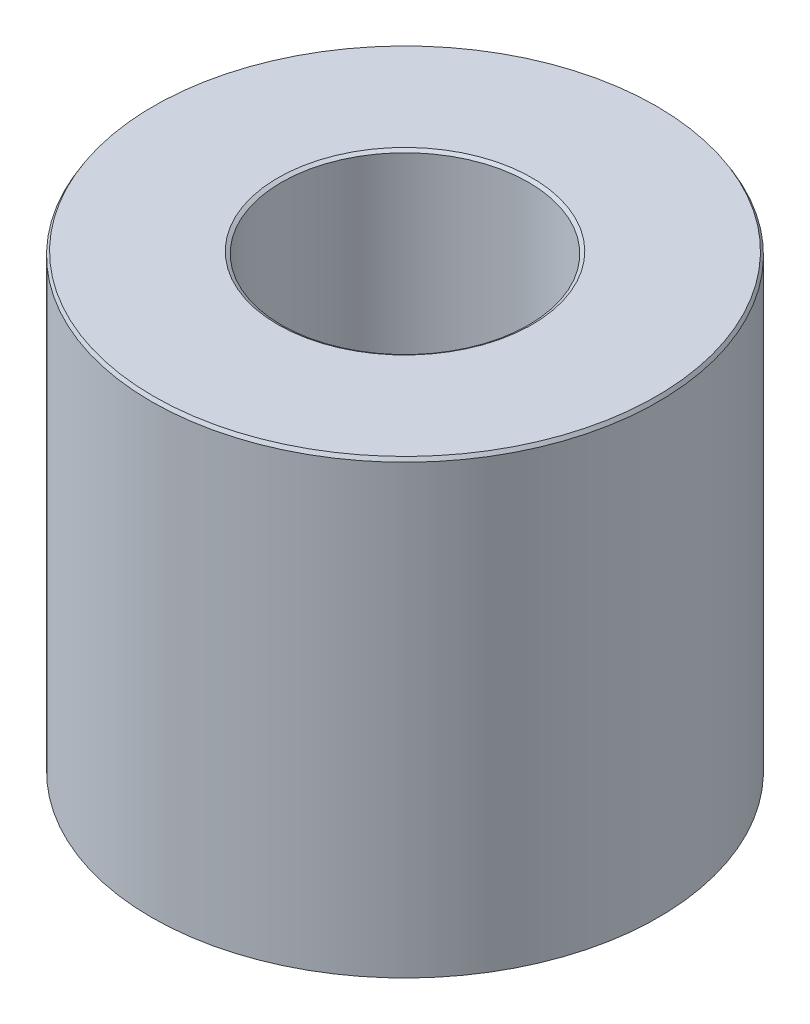
SolidWorks part; units mm, degrees
ref_plane "Front Plane" through (0, 0, 0) normal (0, 0, 1) x (1, 0, 0)
ref_plane "Top Plane" through (0, 0, 0) normal (0, 1, 0) x (1, 0, 0)
ref_plane "Right Plane" through (0, 0, 0) normal (1, 0, 0) x (0, 0, -1)
sketch "Sketch1" plane through (0, 0, 0) normal (0, 1, 0) x (1, 0, 0)
  circle A0 centre (0, 0) radius 50
  dimension "SLEEVE_OD" = 100
extrude "Boss-Extrude1" add sketch "Sketch1" along normal blind 89.214
sketch "Sketch2" plane through (0, 0, 0) normal (0, 1, 0) x (1, 0, 0)
  circle A0 centre (0, 0) radius 24.382
  dimension "BORE_D" = 48.764
extrude "Cut-Extrude1" cut sketch "Sketch2" along normal through all
chamfer "Chamfer1" distance 0.6933 angle 31.278 4 edges at (0, 89.214, 24.382) (0, 0, 24.382) (0, 0, 50) (0, 89.214, 50) first distance on face at (0, 89.214, 24.382) first distance on face at (0, 0, 24.382) first distance on face at (0, 89.214, 50)
